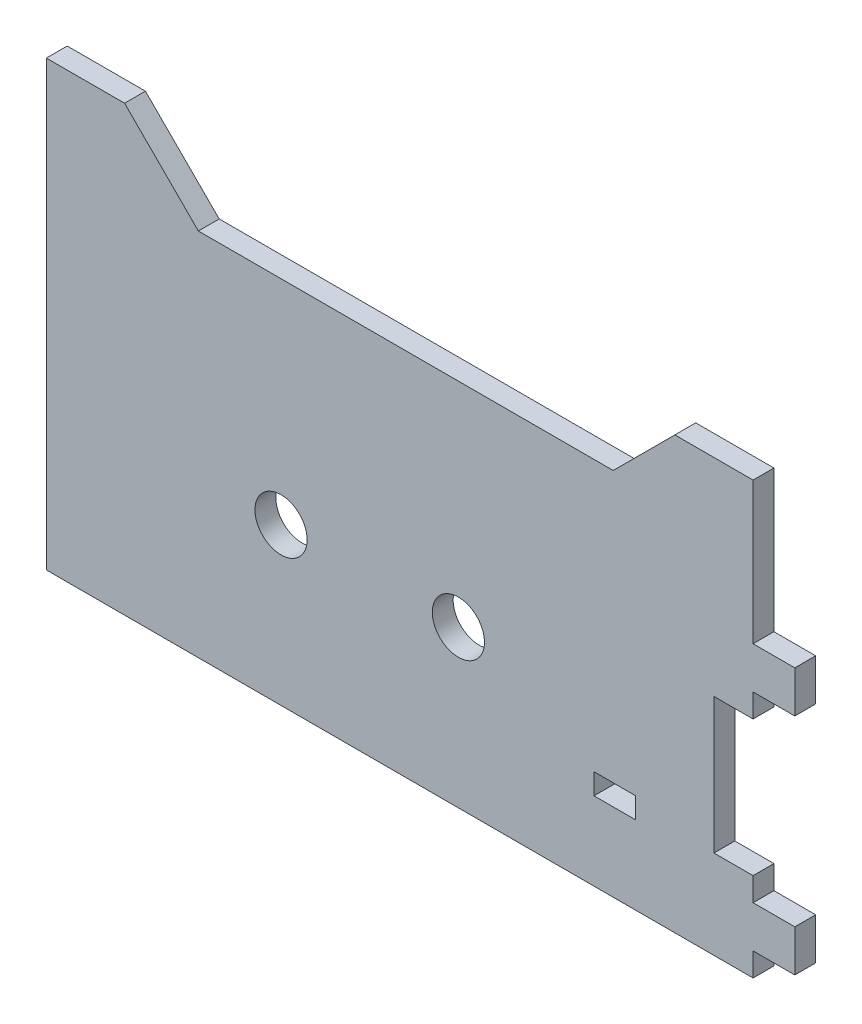
SolidWorks part; units mm, degrees
ref_plane "Front Plane" through (0, 0, 0) normal (0, 0, 1) x (1, 0, 0)
ref_plane "Top Plane" through (0, 0, 0) normal (0, 1, 0) x (1, 0, 0)
ref_plane "Right Plane" through (0, 0, 0) normal (1, 0, 0) x (0, 0, -1)
sketch "Sketch1" plane through (0, 0, 0) normal (0, 0, 1) x (1, 0, 0)
  line L0 (49, 30) -> (56.5, 30)
  line L1 (-79, -30) -> (49, -30)
  line L2 (-79, -30) -> (-79, 30)
  line L3 (-79, 30) -> (49, 30)
  line L6 (56.5, 13) -> (49, 13)
  line L7 (49, 13) -> (49, -13)
  line L8 (49, -13) -> (56.5, -13)
  line L10 (56.5, -30) -> (49, -30)
  line L11 (56.5, 30) -> (56.5, 13) construction
  line L12 (56.5, -13) -> (56.5, -30) construction
  line L13 (56.5, 30) -> (56.5, 25.5)
  line L14 (56.5, 25.5) -> (64.5, 25.5)
  line L15 (64.5, 25.5) -> (64.5, 17.5)
  line L16 (64.5, 17.5) -> (56.5, 17.5)
  line L17 (56.5, 17.5) -> (56.5, 13)
  line L18 (56.5, -13) -> (56.5, -17.5)
  line L19 (56.5, -17.5) -> (64.5, -17.5)
  line L20 (64.5, -17.5) -> (64.5, -25.5)
  line L21 (64.5, -25.5) -> (56.5, -25.5)
  line L22 (56.5, -25.5) -> (56.5, -30)
  line L24 (26, -11) -> (34, -11)
  line L25 (26, -11) -> (26, -15)
  line L26 (26, -15) -> (34, -15)
  line L27 (34, -11) -> (34, -15)
  circle A0 centre (0, 0) radius 5
  circle A3 centre (-34, 0) radius 5
  point P1 (0, 0)
  point P8 (-79, 0)
  dimension "D3" = 128
  dimension "D4" = 0
  dimension "D5" = 10
  dimension "D1" = 45
  dimension "D7" = 0
  dimension "D2" = 60
  dimension "D6" = 34
  dimension "D8" = 26
  dimension "D9" = 17
  dimension "D10" = 7.5
  dimension "D11" = 8
  dimension "D12" = 8
  dimension "D13" = 8
  dimension "D14" = 4
  dimension "D15" = 15
  dimension "D16" = 15
extrude "Boss-Extrude1" add sketch "Sketch1" along normal blind 4
sketch "Sketch2" plane through (0, 0, 0) normal (0, 0, 1) x (1, 0, 0)
  line L0 (-79, 30) -> (56.5, 30)
  line L1 (56.5, 30) -> (56.5, 52.6779)
  line L2 (56.5, 52.6779) -> (41.5, 52.6779)
  line L3 (41.5, 52.6779) -> (29.6799, 40.8579)
  line L4 (29.6799, 40.8579) -> (-49.8579, 40.8579)
  line L5 (-49.8579, 40.8579) -> (-64, 55)
  line L6 (-64, 55) -> (-79, 55)
  line L7 (-79, 55) -> (-79, 30)
  dimension "D1" = 25
  dimension "D2" = 15
  dimension "D3" = 20
  dimension "D4" = 135
extrude "Boss-Extrude2" add sketch "Sketch2" along normal blind 4
